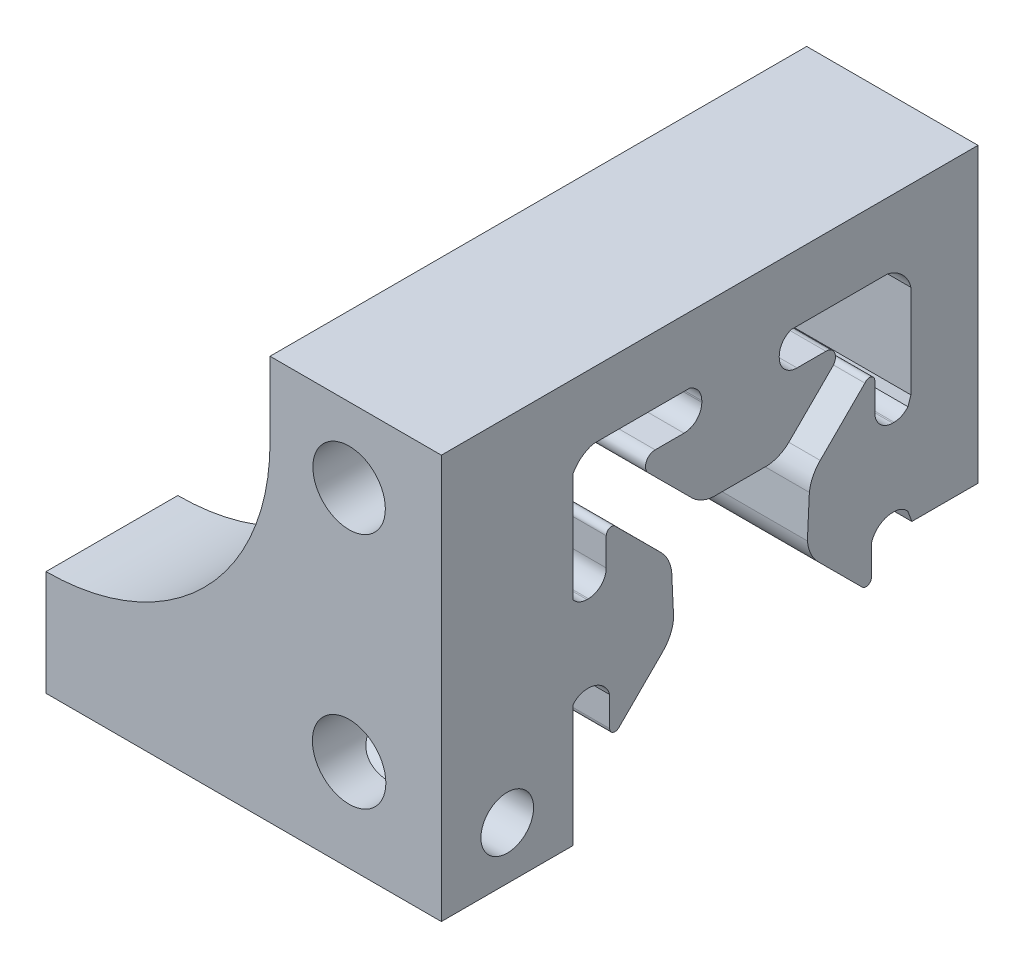
SolidWorks part; units mm, degrees
ref_plane "Front Plane" through (0, 0, 0) normal (0, 0, 1) x (1, 0, 0)
ref_plane "Top Plane" through (0, 0, 0) normal (0, 1, 0) x (1, 0, 0)
ref_plane "Right Plane" through (0, 0, 0) normal (1, 0, 0) x (0, 0, -1)
sketch "bf12_support" plane through (0, 0, 0) normal (0, 0, 1) x (1, 0, 0)
  line L0 (13, 32.5) -> (13, 43) construction
  line L1 (0, 0) -> (60, 0) construction
  line L2 (0, 0) -> (0, 32.5) construction
  line L3 (0, 32.5) -> (13, 32.5) construction
  line L4 (60, 0) -> (60, 32.5) construction
  line L5 (13, 43) -> (47, 43) construction
  line L6 (47, 43) -> (47, 32.5) construction
  line L7 (47, 32.5) -> (60, 32.5) construction
  line L8 (7, 25) -> (7, 32.5) construction
  line L9 (7, 25) -> (0, 25) construction
  line L10 (0, 0) -> (0, 7) construction
  line L11 (0, 7) -> (7, 7) construction
  line L12 (30, 45.9464) -> (30, -5.785) construction
  line L13 (30, 43) -> (30, 25) construction
  circle A0 centre (7, 25) radius 2.75 construction
  circle A1 centre (7, 7) radius 2.7882 construction
  circle A2 centre (53, 7) radius 2.7882 construction
  circle A3 centre (53, 25) radius 2.75 construction
  circle A4 centre (30, 25) radius 13 construction
  point P15 (30, 43)
  dimension "D8" = 5.5
  dimension "D1" = 32.5
  dimension "D2" = 60
  dimension "D3" = 13
  dimension "D4" = 34
  dimension "D5" = 10.5
  dimension "D6" = 7
  dimension "D7" = 7.5
  dimension "D9" = 7
  dimension "D10" = 7
sketch "Sketch7" plane through (0, 0, 0) normal (0, 0, 1) x (1, 0, 0)
  line L0 (30, 8) -> (30, 0)
  line L1 (60, 0) -> (60, 32.5) construction
  line L2 (0, 0) -> (60, 0) construction
  line L6 (60, 0) -> (60, 32.5)
  line L7 (30, 0) -> (60, 0)
  line L11 (47, 32.5) -> (47, 25)
  line L21 (60, 32.5) -> (47, 32.5)
  circle A2 centre (53, 7) radius 2.7882 construction
  circle A3 centre (53, 25) radius 2.75 construction
  circle A6 centre (53, 7) radius 2.7882
  circle A7 centre (53, 25) radius 2.75
  arc A11 (30, 8) -> (47, 25) centre (30, 25) ccw
  dimension "D1" = 18
extrude "Boss-Extrude1" add sketch "Sketch7" along normal blind 5 and the other way blind 5
sketch "Sketch8" plane through (60, 0, 0) normal (1, 0, 0) x (0, 0, -1)
  line L16 (30.3998, 16.9875) -> (30.3998, 18.251) construction
  line L17 (30.3316, 19.0979) -> (30.3316, 22.2518) construction
  line L18 (27.2518, 25.3316) -> (23.6549, 25.3316) construction
  line L19 (22.9494, 25.4) -> (21.9875, 25.4) construction
  line L20 (20.9385, 24.351) -> (20.9385, 24.2392) construction
  line L21 (21.9875, 23.1902) -> (24.1768, 23.1902) construction
  line L22 (24.907, 21.4244) -> (21.5983, 18.1232) construction
  line L23 (18.5582, 17.2976) -> (16.0364, 17.2976) construction
  line L24 (13.8017, 18.1232) -> (10.493, 21.4244) construction
  line L31 (6.049, 15.9385) -> (6.1608, 15.9385) construction
  line L32 (7.2098, 16.9875) -> (7.2098, 19.1021) construction
  line L33 (8.4968, 19.5077) -> (11.8656, 16.1465) construction
  line L34 (12.7764, 14.2695) -> (12.9263, 11.1237) construction
  line L35 (12.0028, 9.1159) -> (8.6977, 5.8183) construction
  line L36 (7.4702, 6.2979) -> (7.4702, 8.4919) construction
  line L37 (6.1608, 9.4612) -> (6.0494, 9.4612) construction
  line L44 (5, 0) -> (5, 32.5) construction
  line L45 (5, 0) -> (5, 16.9875) construction
  line L46 (4.832, 22.6358) -> (4.832, 18.5384) construction
  line L47 (7.7702, 6.2979) -> (7.7702, 8.5345)
  line L48 (6.1608, 9.7612) -> (6.0493, 9.7612)
  line L72 (30.6316, 16.7943) -> (30.6316, 23.8618)
  line L73 (28.8618, 25.6316) -> (21.5633, 25.6316)
  line L75 (20.6385, 24.351) -> (20.6385, 24.2392)
  line L76 (21.9875, 22.8902) -> (24.1768, 22.8902)
  line L77 (24.6951, 21.6367) -> (21.3864, 18.3355)
  line L79 (14.0136, 18.3355) -> (10.7049, 21.6367)
  line L86 (6.049, 15.6385) -> (6.1608, 15.6385)
  line L87 (7.5098, 16.9875) -> (7.5098, 19.1021)
  line L88 (8.2636, 19.3166) -> (11.6537, 15.9342)
  line L89 (12.4773, 14.2446) -> (12.6257, 11.1284)
  line L90 (11.7909, 9.3283) -> (8.4808, 6.0257)
  line L91 (11.9037, -0.3) -> (13.4123, -0.3) construction
  line L92 (14.7613, 1.049) -> (14.7613, 1.1608) construction
  line L93 (13.4123, 2.5098) -> (11.2834, 2.5098) construction
  line L94 (20.6383, 1.1608) -> (20.6383, 1.049) construction
  line L95 (21.9874, -0.3) -> (23.4965, -0.3) construction
  line L96 (23.9044, -0.2316) -> (25.5062, -0.2316) construction
  line L97 (24.1163, 2.2098) -> (21.9874, 2.2098) construction
  line L98 (20.9383, 1.1608) -> (20.9383, 1.049) construction
  line L99 (21.9874, 0) -> (23.2509, 0) construction
  line L100 (24.0977, 0.0684) -> (25.0772, 0.0684) construction
  line L101 (12.1519, 0) -> (13.4123, 0) construction
  line L102 (14.4613, 1.049) -> (14.4613, 1.1608) construction
  line L103 (13.4123, 2.2098) -> (11.2834, 2.2098) construction
  line L104 (21.4402, 7.064) -> (24.6676, 3.8425) construction
  line L105 (24.1163, 2.5098) -> (21.9874, 2.5098) construction
  line L106 (15.9906, 7.9042) -> (19.4091, 7.9042) construction
  line L107 (15.9906, 8.2042) -> (19.4091, 8.2042) construction
  line L108 (21.6521, 7.2763) -> (24.8795, 4.0548) construction
  line L109 (10.7321, 3.8425) -> (13.9595, 7.064) construction
  line L110 (10.5202, 4.0548) -> (13.7476, 7.2763) construction
  line L111 (7.7787, -0.2542) -> (11.4969, -0.2542) construction
  line L112 (8.1466, 0.0458) -> (11.2847, 0.0458) construction
  line L113 (25.7976, 5.7367) -> (28.6701, 8.9952) construction
  line L114 (29.1397, 9.0508) -> (30.6995, 8.4419) construction
  line L115 (25.8135, 6.2084) -> (28.4238, 9.1696) construction
  line L116 (29.3069, 9.3076) -> (30.2602, 8.9355) construction
  line L117 (5.0087, 6.3817) -> (5.0651, 3.1659) construction
  line L118 (4.7023, 6.7442) -> (4.7719, 2.7749) construction
  line L119 (4.7, 8.4117) -> (4.7001, 6.9925) construction
  line L120 (5, 8.4117) -> (5.0001, 7.3604) construction
  line L121 (4.7, 18.1462) -> (4.7, 16.9875) construction
  line L122 (11.9463, 25.6483) -> (7.8384, 25.6484) construction
  line L123 (13.4117, 25.7) -> (12.1567, 25.7) construction
  line L124 (30.6995, 8.4419) -> (35.7198, 8.4419)
  line L125 (35.7198, 8.4419) -> (35.7198, 25.681)
  line L126 (35.7198, 25.681) -> (35.7198, 30.6516)
  line L127 (35.7198, 30.6516) -> (5, 30.6516)
  line L129 (5, 9.2601) -> (5, 16.1393)
  line L131 (5, 30.6516) -> (5, 24.4558)
  line L132 (12.3592, 19.9861) -> (23.0408, 19.9861) construction
  line L133 (17.7, 19.9861) -> (17.7, 14.2932) construction
  line L134 (16.0246, 17.5976) -> (19.3754, 17.5976)
  line L135 (18.5974, 17.5976) -> (16.0246, 17.5976) construction
  line L136 (30.6316, 18.9045) -> (30.6316, 22.6197) construction
  line L137 (27.6197, 25.6316) -> (23.5216, 25.6316) construction
  line L138 (23.1312, 25.7) -> (21.9875, 25.7) construction
  line L139 (13.4125, 23.1902) -> (11.2232, 23.1902) construction
  line L140 (5, 17.9091) -> (5, 16.9875) construction
  line L141 (5.132, 22.2916) -> (5.132, 18.6793) construction
  line L142 (14.3388, 24.141) -> (14.4607, 24.3418) construction
  line L143 (14.6735, 24.1142) -> (14.7571, 24.252) construction
  line L144 (13.4117, 25.4) -> (12.2512, 25.4) construction
  line L145 (11.9103, 25.3483) -> (8.2058, 25.3484) construction
  line L146 (14.4615, 24.351) -> (14.4615, 24.2392) construction
  line L147 (12.4506, 25.4) -> (13.4125, 25.4) construction
  line L148 (8.1482, 25.3316) -> (11.7451, 25.3316) construction
  line L149 (13.4125, 22.8902) -> (11.2232, 22.8902)
  line L150 (14.7615, 24.351) -> (14.7615, 24.2392)
  line L151 (6.5382, 25.6316) -> (13.8367, 25.6316)
  line L152 (11.0916, 22.3328) -> (13.4125, 22.3328) construction
  line L153 (11.1215, 22.6328) -> (13.4105, 22.6328) construction
  line L154 (29.3508, 9.7615) -> (29.2391, 9.7615) construction
  line L155 (29.2392, 9.7612) -> (29.3507, 9.7612)
  line L156 (27.6298, 6.2979) -> (27.6298, 8.5345)
  line L157 (26.4578, 6.1182) -> (23.4111, 9.1579) construction
  line L158 (23.4111, 16.2421) -> (26.7212, 19.5446) construction
  line L159 (27.7848, 19.162) -> (27.89, 16.988) construction
  line L160 (26.1928, 5.9588) -> (23.2076, 8.9372) construction
  line L161 (23.2076, 16.4628) -> (26.5093, 19.7569) construction
  line L162 (28.0841, 19.1829) -> (28.1901, 16.9947) construction
  line L163 (22.5083, 11.1068) -> (22.5083, 14.2932) construction
  line L164 (22.2083, 11.1068) -> (22.2083, 14.2932) construction
  line L165 (27.89, 8.4125) -> (27.89, 6.2979) construction
  line L166 (29.3508, 9.4615) -> (29.2391, 9.4615) construction
  line L167 (28.19, 8.4125) -> (28.19, 6.2979) construction
  line L168 (29.2391, 15.6385) -> (29.3508, 15.6385) construction
  line L169 (29.2391, 15.9385) -> (29.3508, 15.9385) construction
  line L170 (23.6091, 9.3283) -> (26.9192, 6.0257)
  line L171 (22.9227, 14.2446) -> (22.7743, 11.1284)
  line L172 (27.1364, 19.3166) -> (23.7463, 15.9342)
  line L173 (27.8902, 16.9875) -> (27.8902, 19.1021)
  line L174 (29.351, 15.6385) -> (29.2392, 15.6385)
  line L176 (30.4, 16.1393) -> (30.6316, 16.7943)
  line L177 (30.4, 9.2601) -> (30.6995, 8.4419)
  line L179 (30.6998, 16.9875) -> (30.6998, 18.4966) construction
  arc A20 (30.3316, 19.0979) -> (30.3998, 18.251) centre (30.6434, 18.6968) ccw construction
  arc A21 (30.3995, 23.2463) -> (30.3316, 22.2518) centre (30.4636, 22.7423) ccw construction
  arc A22 (30.3995, 23.2463) -> (28.2463, 25.3995) centre (28.2918, 23.2918) ccw construction
  arc A23 (27.2518, 25.3316) -> (28.2463, 25.3995) centre (27.7424, 25.4636) ccw construction
  arc A24 (22.9494, 25.4) -> (23.6549, 25.3316) centre (23.3373, 25.728) ccw construction
  arc A25 (21.9875, 25.4) -> (20.9385, 24.351) centre (21.9875, 24.351) ccw construction
  arc A26 (20.9385, 24.2392) -> (21.9875, 23.1902) centre (21.9875, 24.2392) ccw construction
  arc A27 (24.907, 21.4244) -> (24.1768, 23.1902) centre (24.1768, 22.1563) ccw construction
  arc A29 (13.8017, 18.1232) -> (16.0364, 17.2976) centre (15.8182, 20.1443) ccw construction
  arc A38 (5, 16.9875) -> (6.049, 15.9385) centre (6.049, 16.9875) ccw construction
  arc A39 (6.1608, 15.9385) -> (7.2098, 16.9875) centre (6.1608, 16.9875) ccw construction
  arc A40 (8.4968, 19.5077) -> (7.2098, 19.1021) centre (7.9172, 19.1021) ccw construction
  arc A41 (12.7764, 14.2695) -> (11.8656, 16.1465) centre (9.6231, 13.8989) ccw construction
  arc A42 (12.0028, 9.1159) -> (12.9263, 11.1237) centre (9.7603, 11.3636) ccw construction
  arc A43 (7.4702, 6.2979) -> (8.6977, 5.8183) centre (8.1776, 6.2979) ccw construction
  arc A44 (7.4702, 8.4919) -> (6.1608, 9.4612) centre (6.1609, 8.0923) ccw construction
  arc A45 (6.0494, 9.4612) -> (5, 8.4117) centre (6.0494, 8.4118) ccw construction
  arc A53 (7.7702, 8.5345) -> (6.1608, 9.7612) centre (6.1609, 8.0923) ccw
  arc A54 (6.0493, 9.7612) -> (5, 9.2601) centre (6.0494, 8.4118) ccw
  arc A83 (30.6316, 23.8618) -> (28.8618, 25.6316) centre (28.2918, 23.2918) ccw
  arc A86 (21.5633, 25.6316) -> (20.6385, 24.351) centre (21.9875, 24.351) ccw
  arc A87 (20.6385, 24.2392) -> (21.9875, 22.8902) centre (21.9875, 24.2392) ccw
  arc A88 (24.6951, 21.6367) -> (24.1768, 22.8902) centre (24.1768, 22.1563) ccw
  arc A90 (14.0136, 18.3355) -> (16.0246, 17.5976) centre (15.8182, 20.1443) ccw
  arc A99 (5, 16.1393) -> (6.049, 15.6385) centre (6.049, 16.9875) ccw
  arc A100 (6.1608, 15.6385) -> (7.5098, 16.9875) centre (6.1608, 16.9875) ccw
  arc A101 (8.2636, 19.3166) -> (7.5098, 19.1021) centre (7.9172, 19.1021) ccw
  arc A102 (12.4773, 14.2446) -> (11.6537, 15.9342) centre (9.6231, 13.8989) ccw
  arc A103 (11.7909, 9.3283) -> (12.6257, 11.1284) centre (9.7603, 11.3636) ccw
  arc A104 (7.7702, 6.2979) -> (8.4808, 6.0257) centre (8.1776, 6.2979) ccw
  arc A105 (11.9037, -0.3) -> (11.4969, -0.2542) centre (11.7044, -0.2404) ccw construction
  arc A106 (13.4123, -0.3) -> (14.7613, 1.049) centre (13.4123, 1.049) ccw construction
  arc A107 (14.7613, 1.1608) -> (13.4123, 2.5098) centre (13.4123, 1.1608) ccw construction
  arc A108 (21.9874, 2.5098) -> (20.6383, 1.1608) centre (21.9874, 1.1608) ccw construction
  arc A109 (20.6383, 1.049) -> (21.9874, -0.3) centre (21.9874, 1.049) ccw construction
  arc A110 (23.9044, -0.2316) -> (23.4965, -0.3) centre (23.6967, -0.2435) ccw construction
  arc A111 (26.5394, 1.6948) -> (25.5062, -0.2316) centre (26.6415, 0.3998) ccw construction
  arc A112 (21.9874, 2.2098) -> (20.9383, 1.1608) centre (21.9874, 1.1608) ccw construction
  arc A113 (20.9383, 1.049) -> (21.9874, 0) centre (21.9874, 1.049) ccw construction
  arc A114 (24.0977, 0.0684) -> (23.2509, 0) centre (23.6967, -0.2435) ccw construction
  arc A115 (12.1519, 0) -> (11.2847, 0.0458) centre (11.7044, -0.2404) ccw construction
  arc A116 (13.4123, 0) -> (14.4613, 1.049) centre (13.4123, 1.049) ccw construction
  arc A117 (14.4613, 1.1608) -> (13.4123, 2.2098) centre (13.4123, 1.1608) ccw construction
  arc A118 (24.1163, 2.5098) -> (24.6676, 3.8425) centre (24.1163, 3.2902) ccw construction
  arc A119 (24.1163, 2.2098) -> (24.8795, 4.0548) centre (24.1163, 3.2902) ccw construction
  arc A120 (21.6521, 7.2763) -> (19.4091, 8.2042) centre (19.4091, 5.0292) ccw construction
  arc A121 (21.4402, 7.064) -> (19.4091, 7.9042) centre (19.4091, 5.0292) ccw construction
  arc A122 (15.9906, 7.9042) -> (13.9595, 7.064) centre (15.9906, 5.0292) ccw construction
  arc A123 (15.9906, 8.2042) -> (13.7476, 7.2763) centre (15.9906, 5.0292) ccw construction
  arc A124 (10.7321, 3.8425) -> (11.2834, 2.5098) centre (11.2834, 3.2902) ccw construction
  arc A125 (10.5202, 4.0548) -> (11.2834, 2.2098) centre (11.2834, 3.2902) ccw construction
  arc A126 (4.7499, 2.5665) -> (7.573, -0.2769) centre (7.1086, 2.0852) ccw construction
  arc A127 (7.7787, -0.2542) -> (7.573, -0.2769) centre (7.656, -0.0862) ccw construction
  arc A128 (5.0016, 2.1244) -> (7.1521, -0.0217) centre (7.1086, 2.0852) ccw construction
  arc A129 (8.1466, 0.0458) -> (7.1521, -0.0217) centre (7.656, -0.0862) ccw construction
  arc A130 (26.3934, 1.9795) -> (25.0772, 0.0684) centre (26.6415, 0.3998) ccw construction
  arc A131 (26.5394, 1.6948) -> (25.7224, 5.5913) centre (24.8046, 3.3649) ccw construction
  arc A132 (25.7976, 5.7367) -> (25.7224, 5.5913) centre (25.5899, 5.7519) ccw construction
  arc A133 (29.1397, 9.0508) -> (28.6701, 8.9952) centre (28.9231, 8.8689) ccw construction
  arc A134 (26.3934, 1.9795) -> (25.7243, 5.2618) centre (24.8046, 3.3649) ccw construction
  arc A135 (25.8135, 6.2084) -> (25.7243, 5.2618) centre (25.5899, 5.7519) ccw construction
  arc A136 (29.3069, 9.3076) -> (28.4238, 9.1696) centre (28.9231, 8.8689) ccw construction
  arc A137 (5.0016, 2.1244) -> (5.0651, 3.1659) centre (4.9609, 2.6495) ccw construction
  arc A138 (4.7499, 2.5665) -> (4.7719, 2.7749) centre (4.9609, 2.6495) ccw construction
  arc A139 (4.7023, 6.7442) -> (4.7001, 6.9925) centre (4.8681, 6.8698) ccw construction
  arc A140 (5.0087, 6.3817) -> (5.0001, 7.3604) centre (4.8681, 6.8698) ccw construction
  arc A141 (6.0493, 9.7612) -> (4.7, 8.4117) centre (6.0494, 8.4118) ccw construction
  arc A142 (4.7, 16.9875) -> (6.049, 15.6385) centre (6.049, 16.9875) ccw construction
  arc A143 (4.7, 18.1462) -> (4.832, 18.5384) centre (4.746, 18.349) ccw construction
  arc A145 (7.633, 25.6717) -> (4.7803, 22.8191) centre (7.1625, 23.2896) ccw construction
  arc A146 (4.832, 22.6358) -> (4.7803, 22.8191) centre (4.9842, 22.7776) ccw construction
  arc A147 (11.9463, 25.6483) -> (12.1567, 25.7) centre (12.0091, 25.8466) ccw construction
  arc A148 (7.633, 25.6717) -> (7.8384, 25.6484) centre (7.7153, 25.4807) ccw construction
  arc A149 (14.7571, 24.252) -> (13.4117, 25.7) centre (13.4117, 24.351) ccw construction
  arc A150 (18.5974, 17.5976) -> (21.3864, 18.3355) centre (19.3558, 20.3708) ccw construction
  arc A151 (18.5582, 17.2976) -> (21.5983, 18.1232) centre (19.3558, 20.3708) ccw construction
  arc A152 (21.3864, 18.3355) -> (19.3754, 17.5976) centre (19.5818, 20.1443) cw
  arc A153 (30.6544, 22.8252) -> (30.6316, 22.6197) centre (30.4636, 22.7423) ccw construction
  arc A154 (30.6316, 18.9045) -> (30.6998, 18.4966) centre (30.6434, 18.6968) ccw construction
  arc A155 (27.6197, 25.6316) -> (27.8252, 25.6544) centre (27.7424, 25.4636) ccw construction
  arc A156 (23.1312, 25.7) -> (23.5216, 25.6316) centre (23.3373, 25.728) ccw construction
  arc A157 (30.6544, 22.8252) -> (27.8252, 25.6544) centre (28.2918, 23.2918) ccw construction
  arc A158 (21.9875, 25.7) -> (20.6385, 24.351) centre (21.9875, 24.351) ccw construction
  arc A159 (5, 17.9091) -> (5.132, 18.6793) centre (4.746, 18.349) ccw construction
  arc A160 (5.132, 22.2916) -> (5.0343, 23.2831) centre (4.9842, 22.7776) ccw construction
  arc A161 (10.493, 21.4244) -> (11.2232, 23.1902) centre (11.2232, 22.1563) cw construction
  arc A162 (13.4125, 22.3328) -> (14.6735, 24.1142) centre (13.3957, 23.6817) ccw construction
  arc A163 (13.4105, 22.6328) -> (14.3388, 24.141) centre (13.3957, 23.6817) ccw construction
  arc A164 (14.4607, 24.3418) -> (13.4117, 25.4) centre (13.4117, 24.351) ccw construction
  arc A165 (11.9103, 25.3483) -> (12.2512, 25.4) centre (12.0091, 25.8466) ccw construction
  arc A166 (7.2113, 25.4172) -> (8.2058, 25.3484) centre (7.7153, 25.4807) ccw construction
  arc A167 (7.2113, 25.4172) -> (5.0343, 23.2831) centre (7.1625, 23.2896) ccw construction
  arc A168 (14.4615, 24.2392) -> (13.4125, 23.1902) centre (13.4125, 24.2392) cw construction
  arc A169 (13.4125, 25.4) -> (14.4615, 24.351) centre (13.4125, 24.351) cw construction
  arc A170 (12.4506, 25.4) -> (11.7451, 25.3316) centre (12.0627, 25.728) cw construction
  arc A171 (10.7049, 21.6367) -> (11.2232, 22.8902) centre (11.2232, 22.1563) cw
  arc A172 (14.7615, 24.2392) -> (13.4125, 22.8902) centre (13.4125, 24.2392) cw
  arc A173 (13.8367, 25.6316) -> (14.7615, 24.351) centre (13.4125, 24.351) cw
  arc A174 (11.0916, 22.3328) -> (10.7049, 21.6367) centre (10.9972, 21.9298) ccw construction
  arc A175 (11.1215, 22.6328) -> (10.493, 21.4244) centre (10.9972, 21.9298) ccw construction
  arc A176 (5, 24.4558) -> (6.5382, 25.6316) centre (7.1082, 23.2918) cw
  arc A177 (26.1928, 5.9588) -> (28.19, 6.2979) centre (27.1626, 6.2979) ccw construction
  arc A178 (26.4578, 6.1182) -> (27.89, 6.2979) centre (27.1626, 6.2979) ccw construction
  arc A179 (27.7848, 19.162) -> (26.7212, 19.5446) centre (27.1626, 19.1021) ccw construction
  arc A180 (27.89, 16.988) -> (29.2391, 15.6385) centre (29.2391, 16.9875) ccw construction
  arc A181 (28.0841, 19.1829) -> (26.5093, 19.7569) centre (27.1626, 19.1021) ccw construction
  arc A182 (28.1901, 16.9947) -> (29.2391, 15.9385) centre (29.2391, 16.9875) ccw construction
  arc A183 (22.5083, 11.1068) -> (23.4111, 9.1579) centre (25.0633, 11.1068) ccw construction
  arc A184 (23.4111, 16.2421) -> (22.5083, 14.2932) centre (25.0633, 14.2932) ccw construction
  arc A185 (22.2083, 11.1068) -> (23.2076, 8.9372) centre (25.0633, 11.1068) ccw construction
  arc A186 (23.2076, 16.4628) -> (22.2083, 14.2932) centre (25.0633, 14.2932) ccw construction
  arc A187 (30.6995, 8.4419) -> (29.3508, 9.7615) centre (29.3508, 8.4125) ccw construction
  arc A188 (29.2391, 9.7615) -> (27.89, 8.4125) centre (29.2391, 8.4125) ccw construction
  arc A189 (30.2602, 8.9355) -> (29.3508, 9.4615) centre (29.3508, 8.4125) ccw construction
  arc A190 (29.2391, 9.4615) -> (28.19, 8.4125) centre (29.2391, 8.4125) ccw construction
  arc A191 (29.3508, 15.6385) -> (30.6998, 16.9875) centre (29.3508, 16.9875) ccw construction
  arc A192 (29.3508, 15.9385) -> (30.3998, 16.9875) centre (29.3508, 16.9875) ccw construction
  arc A193 (29.3507, 9.7612) -> (30.4, 9.2601) centre (29.3506, 8.4118) cw
  arc A194 (27.6298, 8.5345) -> (29.2392, 9.7612) centre (29.2391, 8.0923) cw
  arc A195 (27.6298, 6.2979) -> (26.9192, 6.0257) centre (27.2224, 6.2979) cw
  arc A196 (23.6091, 9.3283) -> (22.7743, 11.1284) centre (25.6397, 11.3636) cw
  arc A197 (22.9227, 14.2446) -> (23.7463, 15.9342) centre (25.7769, 13.8989) cw
  arc A198 (27.1364, 19.3166) -> (27.8902, 19.1021) centre (27.4828, 19.1021) cw
  arc A199 (29.2392, 15.6385) -> (27.8902, 16.9875) centre (29.2392, 16.9875) cw
  arc A200 (30.4, 16.1393) -> (29.351, 15.6385) centre (29.351, 16.9875) cw
  line M102 (5, 0) -> (5, 32.5)
  dimension "D1" = 0.3
extrude "Boss-Extrude2" add sketch "Sketch8" against normal up to surface (13 mm away) contours L79 A90 L77 A88 L76 A87 L75 A86 L73 A83 L72 L124 L125 L126 L127 M102 | L47 A104 L90 A103 L89 A102 L88 A101 L87 A100 L86 A99 A54 L48 A53 M102 region at (60, 21.642, -23.8415) region at (60, 12.6786, -8.8196) up to face at (47, 28.75, 0)
sketch "Sketch14" plane through (0, 0, -5) normal (0, 0, -1) x (-1, 0, 0)
  line L4 (-60, 30.6516) -> (-47, 30.6516)
  line L5 (-47, 30.6516) -> (-47, 32.5)
  line L6 (-47, 32.5) -> (-60, 32.5)
  line L7 (-60, 32.5) -> (-60, 30.6516)
  line L9 (-47, 30.6516) -> (-47, 32.5)
  line L10 (-47, 32.5) -> (-60, 32.5)
  line L11 (-60, 32.5) -> (-60, 30.6516)
  line L12 (-60, 30.6516) -> (-47, 30.6516)
  dimension "D1" = 0
extrude "Cut-Extrude3" cut sketch "Sketch14" against normal up to next
sketch "Sketch15" plane through (30, 0, 0) normal (-1, 0, 0) x (0, 0, 1)
  line L0 (0, 8) -> (0, 0) construction
  line L4 (-5, 0) -> (5, 0)
  line L5 (5, 0) -> (5, 8)
  line L6 (5, 8) -> (-5, 8)
  line L7 (-5, 8) -> (-5, 0)
  line L8 (-5, 0) -> (5, 0) construction
  line L9 (5, 0) -> (5, 8) construction
  line L10 (5, 8) -> (-5, 8) construction
  line L11 (-5, 8) -> (-5, 0) construction
  circle A0 centre (0, 4) radius 1.45
  dimension "D2" = 2.9
  dimension "D1" = 0
extrude "Cut-Extrude4" cut sketch "Sketch15" against normal blind 3
sketch "Sketch16" plane through (33, 0, 0) normal (-1, 0, 0) x (0, 0, 1)
  circle A0 centre (0, 4) radius 2
  dimension "D1" = 4
extrude "Cut-Extrude5" cut sketch "Sketch16" against normal up to next
ref_plane "Plane1" through (30, 0, 0) normal (-1, 0, 0) x (0, 0, 1)
fillet "Fillet1" radius 0.5 1 edges at (33, 2, 0)
